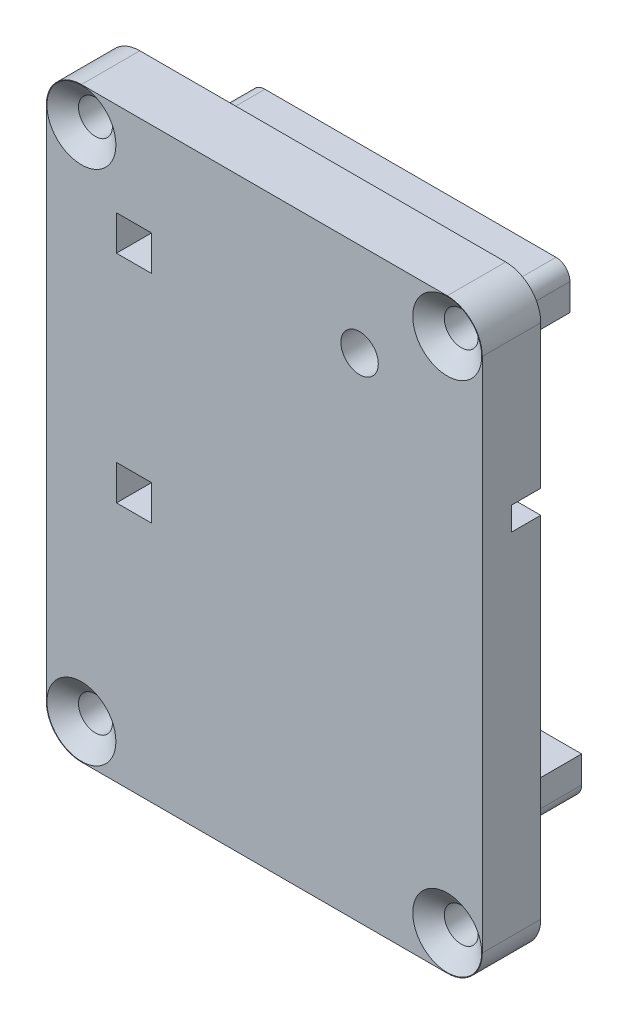
SolidWorks part; units mm, degrees
ref_plane "정면" through (0, 0, 0) normal (0, 0, 1) x (1, 0, 0)
ref_plane "윗면" through (0, 0, 0) normal (0, 1, 0) x (1, 0, 0)
ref_plane "우측면" through (0, 0, 0) normal (1, 0, 0) x (0, 0, -1)
sketch "스케치1" plane through (0, 0, 0) normal (0, 0, 1) x (1, 0, 0)
  line L1 (-18.65, 25.1) -> (18.65, 25.1)
  line L2 (-18.65, 25.1) -> (-18.65, -25.1)
  line L3 (-18.65, -25.1) -> (18.65, -25.1)
  line L4 (18.65, 25.1) -> (18.65, -25.1)
  line L5 (-18.65, 25.1) -> (18.65, -25.1) construction
  line L6 (-18.65, -25.1) -> (18.65, 25.1) construction
  point P0 (0, 0)
  dimension "D1" = 37.3
  dimension "D2" = 50.2
extrude "보스-돌출1" add sketch "스케치1" along normal blind 5
sketch "스케치2" plane through (0, 0, 0) normal (0, 0, 1) x (1, 0, 0)
  line L0 (13.65, 16.6) -> (-13.65, 16.6)
  line L1 (13.65, -20.1) -> (-13.65, -20.1)
  line L2 (13.65, -20.1) -> (13.65, -16.6)
  line L3 (13.65, 20.1) -> (-13.65, 20.1)
  line L4 (-13.65, -20.1) -> (-13.65, -16.6)
  line L5 (13.65, -20.1) -> (-13.65, 20.1) construction
  line L6 (13.65, 20.1) -> (-13.65, -20.1) construction
  line L7 (13.65, -16.6) -> (-13.65, -16.6)
  line L8 (-13.65, 16.6) -> (-13.65, 20.1)
  line L9 (13.65, 16.6) -> (13.65, 20.1)
  point P0 (0, 0)
  dimension "D1" = 27.3
  dimension "D2" = 40.2
  dimension "D3" = 3.5
  dimension "D4" = 3.5
extrude "보스-돌출2" add sketch "스케치2" against normal blind 8.5 contours L2 L7 L4 L1 region at (0, -18.35, 0)
extrude "보스-돌출3" add sketch "스케치2<3>" against normal blind 7.5 contours L0 L9 L3 L8 region at (0, 18.35, 0)
sketch "스케치2<3>" plane through (0, 0, 0) normal (0, 0, 1) x (1, 0, 0) same geometry as "스케치2"
fillet "필렛1" radius 1.2 4 edges at (-13.65, -20.1, -4.25) (13.65, -20.1, -4.25) (13.65, 20.1, -3.75) (-13.65, 20.1, -3.75)
fillet "필렛2" radius 3 4 edges at (18.65, -25.1, 2.5) (-18.65, -25.1, 2.5) (-18.65, 25.1, 2.5) (18.65, 25.1, 2.5)
sketch "스케치4" plane through (0, 0, 5) normal (0, 0, 1) x (1, 0, 0)
  line L0 (15.65, 25.1) -> (-15.65, 25.1) construction
  line L1 (18.65, -22.1) -> (18.65, 22.1) construction
  circle A0 centre (8.15, 17.1) radius 1.6
  dimension "D1" = 3.2
  dimension "D2" = 8
  dimension "D3" = 10.5
extrude "컷-돌출1" cut sketch "스케치4" against normal through all both and the other way through all
sketch "스케치5" plane through (0, 0, -7.5) normal (0, 0, -1) x (-1, 0, 0)
  line L1 (-10.4, 14.85) -> (-5.9, 14.85)
  line L2 (-10.4, 14.85) -> (-10.4, 19.35)
  line L3 (-10.4, 19.35) -> (-5.9, 19.35)
  line L4 (-5.9, 14.85) -> (-5.9, 19.35)
  line L5 (-10.4, 14.85) -> (-5.9, 19.35) construction
  line L6 (-10.4, 19.35) -> (-5.9, 14.85) construction
  point P0 (-8.15, 17.1)
  dimension "D1" = 4.5
  dimension "D2" = 4.5
extrude "컷-돌출2" cut sketch "스케치5" against normal blind 1.5
sketch "스케치6" plane through (0, 0, 5) normal (0, 0, 1) x (1, 0, 0)
  circle A0 centre (-15.65, 22.1) radius 1.45
  circle A1 centre (15.65, 22.1) radius 1.45
  circle A2 centre (15.65, -22.1) radius 1.45
  circle A3 centre (-15.65, -22.1) radius 1.45
  dimension "D1" = 2.9
  dimension "D2" = 2.9
  dimension "D3" = 2.9
  dimension "D4" = 2.9
extrude "컷-돌출3" cut sketch "스케치6" against normal through all
chamfer "모따기1" distance 1.5 distance2 1.2 4 edges at (17.1, -22.1, 5) (-14.2, -22.1, 5) (17.1, 22.1, 5) (-14.2, 22.1, 5) first distance on face at (-14.2, -22.1, 5)
sketch "스케치8" plane through (0, 0, 5) normal (0, 0, 1) x (1, 0, 0)
  line L0 (-12.65, 14.1) -> (-12.65, -1.4) construction
  line L1 (-12.65, 17.1) -> (-9.65, 17.1)
  line L2 (-12.65, 17.1) -> (-12.65, 14.1)
  line L3 (-12.65, 14.1) -> (-9.65, 14.1)
  line L4 (-9.65, 17.1) -> (-9.65, 14.1)
  line L5 (9.65, 17.1) -> (12.65, 17.1) construction
  line L6 (9.65, 17.1) -> (9.65, 13.1) construction
  line L7 (9.65, 13.1) -> (12.65, 13.1) construction
  line L8 (12.65, 17.1) -> (12.65, 13.1) construction
  line L9 (-12.65, -1.4) -> (-9.65, -1.4)
  line L10 (-12.65, -1.4) -> (-12.65, -4.4)
  line L11 (-12.65, -4.4) -> (-9.65, -4.4)
  line L12 (-9.65, -1.4) -> (-9.65, -4.4)
  line L13 (-9.65, 17.1) -> (9.65, 17.1)
  line L14 (12.45, 20.1) -> (-12.45, 20.1) construction
  line L15 (18.65, -22.1) -> (18.65, 22.1) construction
  line L16 (-18.65, 22.1) -> (-18.65, -22.1) construction
  dimension "D1" = 3
  dimension "D2" = 3
  dimension "D3" = 4
  dimension "D4" = 3
  dimension "D5" = 3
  dimension "D6" = 3
  dimension "D7" = 3
  dimension "D8" = 15.5
  dimension "D9" = 6
  dimension "6" = 6
extrude "컷-돌출4" cut sketch "스케치8" against normal blind 5 contours L4 L1 L2 L3 | L12 L9 L10 L11 region at (-11.15, 15.6, 5) region at (-11.15, -2.9, 5)
sketch "스케치9" plane through (0, 0, -7.5) normal (0, 0, -1) x (-1, 0, 0)
  line L1 (0, 9.8335) -> (-20.0339, 9.8335)
  line L2 (0, 9.8335) -> (0, 7.8335)
  line L3 (0, 7.8335) -> (-20.0339, 7.8335)
  line L4 (-20.0339, 9.8335) -> (-20.0339, 7.8335)
  line L5 (0, 7.8335) -> (0, 0) construction
  dimension "D1" = 2
extrude "컷-돌출5" cut sketch "스케치9" against normal blind 10
